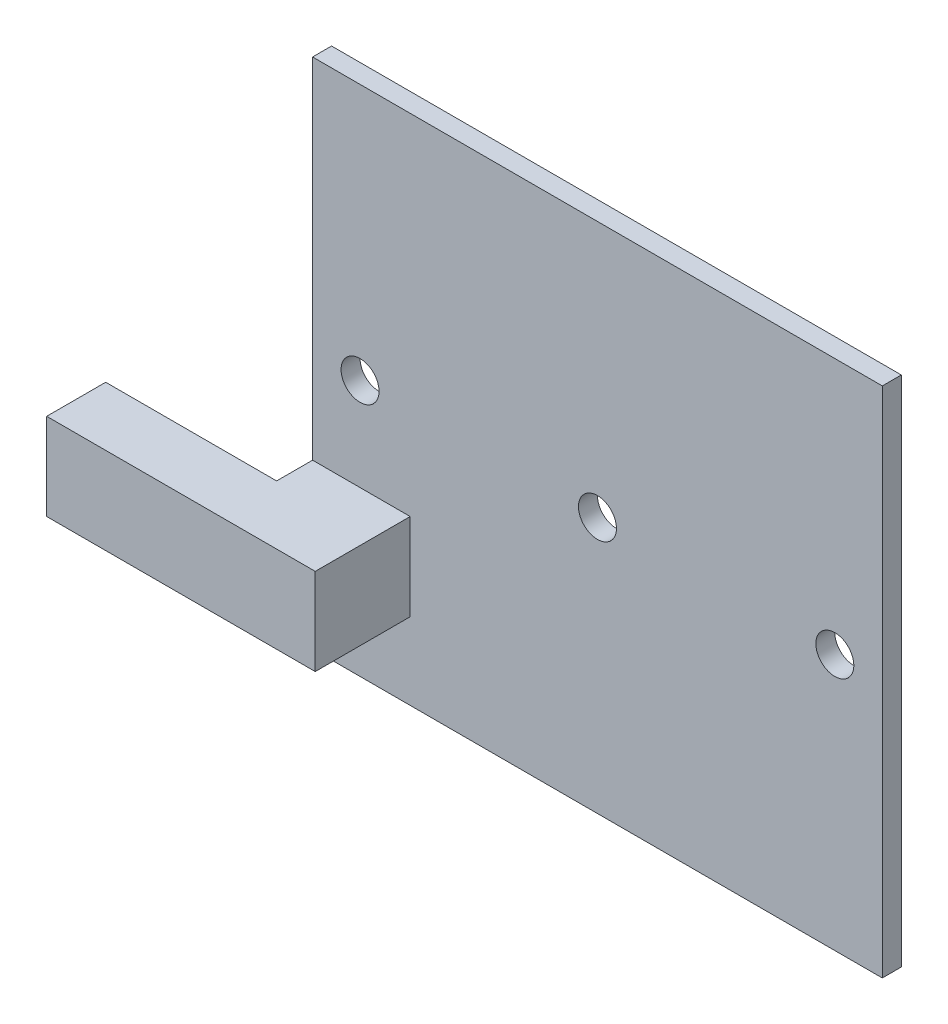
SolidWorks part; units mm, degrees
ref_plane "Plan de face" through (0, 0, 0) normal (0, 0, 1) x (1, 0, 0)
ref_plane "Plan de dessus" through (0, 0, 0) normal (0, 1, 0) x (1, 0, 0)
ref_plane "Plan de droite" through (0, 0, 0) normal (1, 0, 0) x (0, 0, -1)
sketch "Esquisse1" plane through (0, 0, 0) normal (0, 0, 1) x (1, 0, 0)
  line L1 (0, 0) -> (60, 0)
  line L2 (0, 0) -> (0, -54)
  line L3 (0, -54) -> (60, -54)
  line L4 (60, 0) -> (60, -54)
  circle A0 centre (5, -27) radius 2
  circle A1 centre (30, -27) radius 2
  circle A2 centre (55, -27) radius 2
  dimension "D1" = 4
  dimension "D2" = 4
  dimension "D3" = 4
  dimension "D4" = 25
  dimension "D5" = 25
  dimension "D6" = 60
  dimension "D7" = 54
  dimension "D8" = 27
  dimension "D9" = 5
  dimension "D10" = 27
  dimension "D11" = 27
extrude "Boss.-Extru.1" add sketch "Esquisse1" along normal blind 2
sketch "Esquisse2" plane through (0, 0, 2) normal (0, 0, 1) x (1, 0, 0)
  line L0 (0, 0) -> (0, -54) construction
  line L1 (0, -45.9135) -> (10.2805, -45.9135)
  line L2 (0, -45.9135) -> (0, -36.7723)
  line L3 (0, -36.7723) -> (10.2805, -36.7723)
  line L4 (10.2805, -45.9135) -> (10.2805, -36.7723)
extrude "Boss.-Extru.2" add sketch "Esquisse2" along normal blind 10
sketch "Esquisse3" plane through (0, 0, 0) normal (-1, 0, 0) x (0, 0, 1)
  line L0 (12, -36.7723) -> (2, -36.7723) construction
  line L1 (12, -45.9135) -> (5.7863, -45.9135)
  line L2 (12, -45.9135) -> (12, -36.7723)
  line L3 (12, -36.7723) -> (5.7863, -36.7723)
  line L4 (5.7863, -45.9135) -> (5.7863, -36.7723)
extrude "Boss.-Extru.3" add sketch "Esquisse3" along normal blind 18
